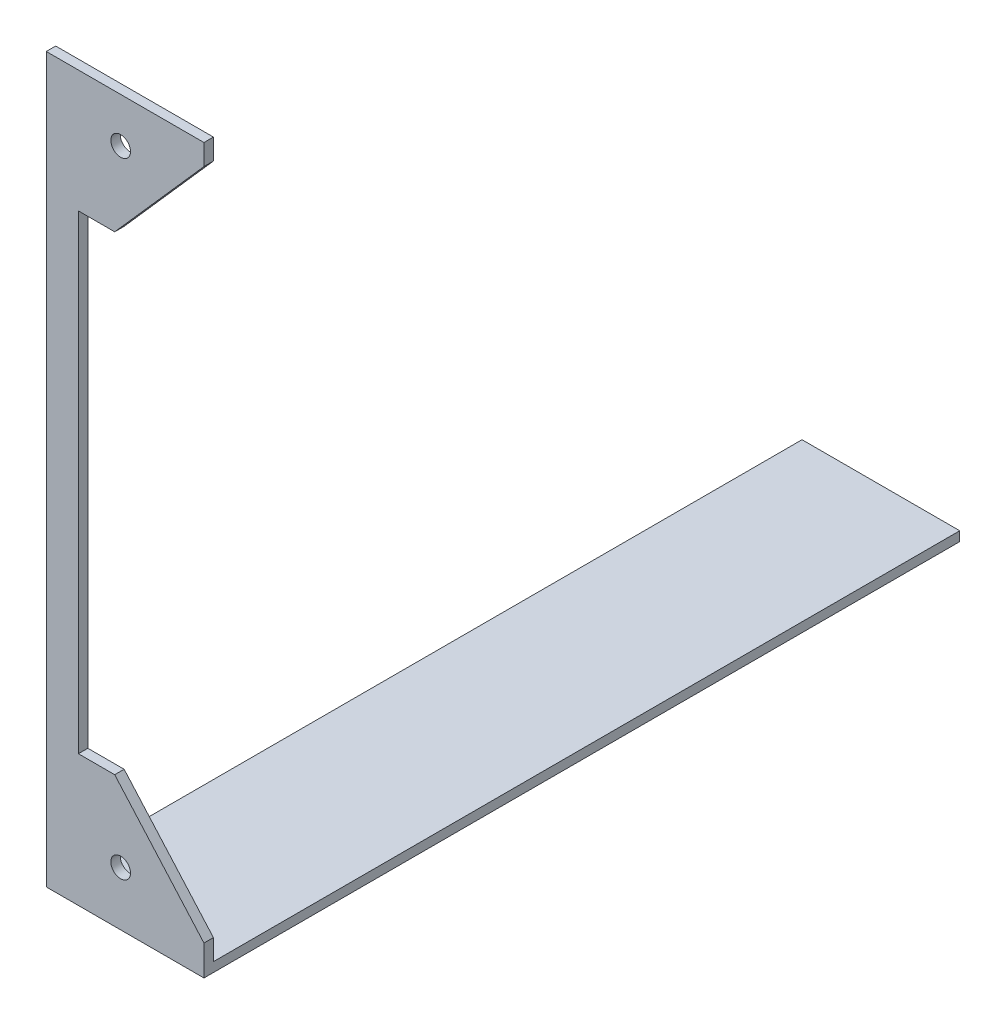
SolidWorks part; units mm, degrees
ref_plane "Front Plane" through (0, 0, 0) normal (0, 0, 1) x (1, 0, 0)
ref_plane "Top Plane" through (0, 0, 0) normal (0, 1, 0) x (1, 0, 0)
ref_plane "Right Plane" through (0, 0, 0) normal (1, 0, 0) x (0, 0, -1)
sketch "Sketch1" plane through (0, 0, 0) normal (0, 0, 1) x (1, 0, 0)
  line L0 (-250, 120) -> (0, 120) construction
  line L1 (-238.5, 99.5) -> (-223.5, 116.5) construction
  line L2 (-244.6, 99.5) -> (-238.5, 99.5) construction
  line L3 (-244.6, 20.5) -> (-244.6, 99.5) construction
  line L4 (-250, 2) -> (-250, 118) construction
  line L5 (0, 0) -> (-250, 0) construction
  line L6 (-238.5, 20.5) -> (-244.6, 20.5) construction
  line L7 (-223.5, 3.5) -> (-238.5, 20.5) construction
  line L8 (-250, 120) -> (-223.5, 120)
  line L9 (-238.5, 99.5) -> (-223.5, 116.5)
  line L10 (-244.6, 99.5) -> (-238.5, 99.5)
  line L11 (-244.6, 20.5) -> (-244.6, 99.5)
  line L12 (-250, 0) -> (-250, 120)
  line L13 (-223.5, 0) -> (-250, 0)
  line L14 (-238.5, 20.5) -> (-244.6, 20.5)
  line L15 (-223.5, 3.5) -> (-238.5, 20.5)
  line L16 (-223.5, 116.5) -> (-223.5, 120)
  line L17 (-223.5, 3.5) -> (-223.5, 0)
  arc A0 (-239.15, 112.5) -> (-235.85, 112.5) centre (-237.5, 112.5) ccw construction
  arc A1 (-235.85, 112.5) -> (-239.15, 112.5) centre (-237.5, 112.5) ccw construction
  arc A2 (-235.85, 7.5) -> (-239.15, 7.5) centre (-237.5, 7.5) ccw construction
  arc A3 (-239.15, 7.5) -> (-235.85, 7.5) centre (-237.5, 7.5) ccw construction
  arc A4 (-239.15, 112.5) -> (-235.85, 112.5) centre (-237.5, 112.5) ccw
  arc A5 (-235.85, 112.5) -> (-239.15, 112.5) centre (-237.5, 112.5) ccw
  arc A6 (-235.85, 7.5) -> (-239.15, 7.5) centre (-237.5, 7.5) ccw
  arc A7 (-239.15, 7.5) -> (-235.85, 7.5) centre (-237.5, 7.5) ccw
extrude "Boss-Extrude1" add sketch "Sketch1" along normal blind 1.5875
sketch "Sketch2" plane through (0, 0, 0) normal (0, 1, 0) x (1, 0, 0)
  line L0 (-223.5, -1.5875) -> (-250, -1.5875)
  line L1 (-250, -1.5875) -> (-250, 125.4125)
  line L2 (-250, 125.4125) -> (-223.5, 125.4125)
  line L3 (-223.5, 125.4125) -> (-223.5, -1.5875)
  dimension "D1" = 127
extrude "Boss-Extrude2" add sketch "Sketch2" against normal blind 1.5875 contours L3 L0 L1 L2
